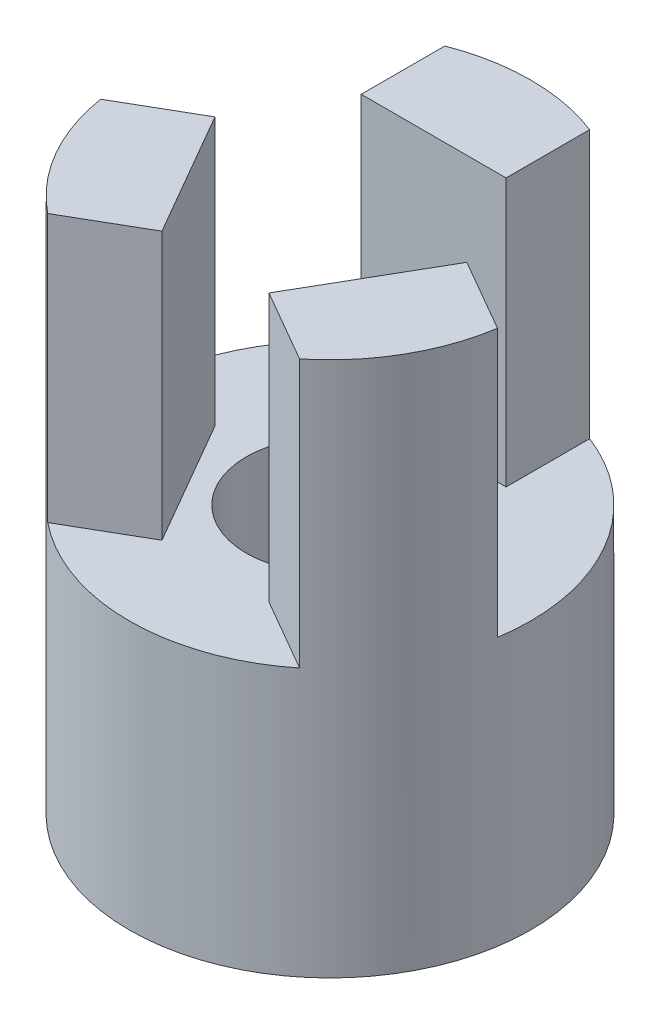
SolidWorks part; units mm, degrees
material "ABS"
ref_plane "Front Plane" through (0, 0, 0) normal (0, 0, 1) x (1, 0, 0)
ref_plane "Top Plane" through (0, 0, 0) normal (0, 1, 0) x (1, 0, 0)
ref_plane "Right Plane" through (0, 0, 0) normal (1, 0, 0) x (0, 0, -1)
sketch "Sketch1" plane through (0, 0, 0) normal (0, 1, 0) x (1, 0, 0)
  line L0 (0, 0) -> (0, -8.6477) construction
  line L1 (-4.7797, -5.9346) -> (0, -3.175)
  line L2 (0, -3.175) -> (4.7797, -5.9346)
  line L3 (-2.7496, 7.1066) -> (-2.7496, 1.5875)
  line L4 (-2.7496, 1.5875) -> (-7.5293, -1.1721)
  line L5 (7.5293, -1.1721) -> (2.7496, 1.5875)
  line L6 (2.7496, 1.5875) -> (2.7496, 7.1066)
  line L7 (-2.0312, -4.3477) -> (2.0312, -4.3477)
  line L8 (-2.7496, 3.933) -> (-4.7809, 0.4148)
  line L9 (4.7809, 0.4148) -> (2.7496, 3.933)
  line L10 (-4.7809, 0.4148) -> (-2.0312, -4.3477)
  line L11 (2.0312, -4.3477) -> (4.7809, 0.4148)
  line L12 (2.7496, 3.933) -> (-2.7496, 3.933)
  circle A0 centre (0, 0) radius 7.62
  circle A1 centre (0, 0) radius 3.175
  point P16 (0, 0)
  point P23 (0, 0)
  dimension "D1" = 6.35
  dimension "D2" = 15.24
  dimension "D3" = 120
  dimension "D4" = 3
  dimension "D5" = 3
extrude "Boss-Extrude1" add sketch "Sketch1" along normal blind 10.16 contours A1 L2 A0 L5 | A1 L4 A0 L1 | A1 L6 A0 L3 region at (-4.9324, 0, 2.8477) region at (4.9324, 0, 2.8477) region at (0, 0, -5.6954)
extrude "Boss-Extrude2" add sketch "Sketch1<4>" against normal blind 10.16 contours A1 L4 L10 L1 | L3 L8 L4 | A1 L6 L12 L3 | L5 L9 L6 | A1 L2 L11 L5 | L2 L0 L7 | L0 L1 L7 | L0 L7 L1 A0 | L4 A0 L1 L10 | L3 A0 L4 L8 | L6 A0 L3 L12 | L5 A0 L6 L9 | L2 A0 L5 L11 | L7 L0 A0 L2 region at (0.6771, 0, 3.9568) region at (-0.6771, 0, 3.9568) region at (2.8076, 0, 1.621) region at (-2.8076, 0, 1.621) region at (1.8088, 0, 5.9379) region at (-1.8088, 0, 5.9379) region at (-4.9324, 0, 2.8477) region at (4.9324, 0, 2.8477) region at (-3.4267, 0, -1.9784) region at (0, 0, -3.2419) region at (-5.1423, 0, -2.9689) region at (5.1423, 0, -2.9689) region at (3.4267, 0, -1.9784) region at (0, 0, -5.6954)
sketch "Sketch1<4>" plane through (0, 0, 0) normal (0, 1, 0) x (1, 0, 0) same geometry as "Sketch1"
sketch "Sketch2" plane through (0, -10.16, 0) normal (0, -1, 0) x (1, 0, 0)
  line L1 (6.35, 0) -> (3.175, 5.4993)
  line L2 (3.175, 5.4993) -> (-3.175, 5.4993)
  line L3 (-3.175, 5.4993) -> (-6.35, 0)
  line L4 (-6.35, 0) -> (-3.175, -5.4993)
  line L5 (-3.175, -5.4993) -> (3.175, -5.4993)
  line L6 (3.175, -5.4993) -> (6.35, 0)
  circle A0 centre (0, 0) radius 5.4993 construction
  dimension "D1" = 6.35
extrude "Cut-Extrude1" cut sketch "Sketch2" against normal blind 3.302
